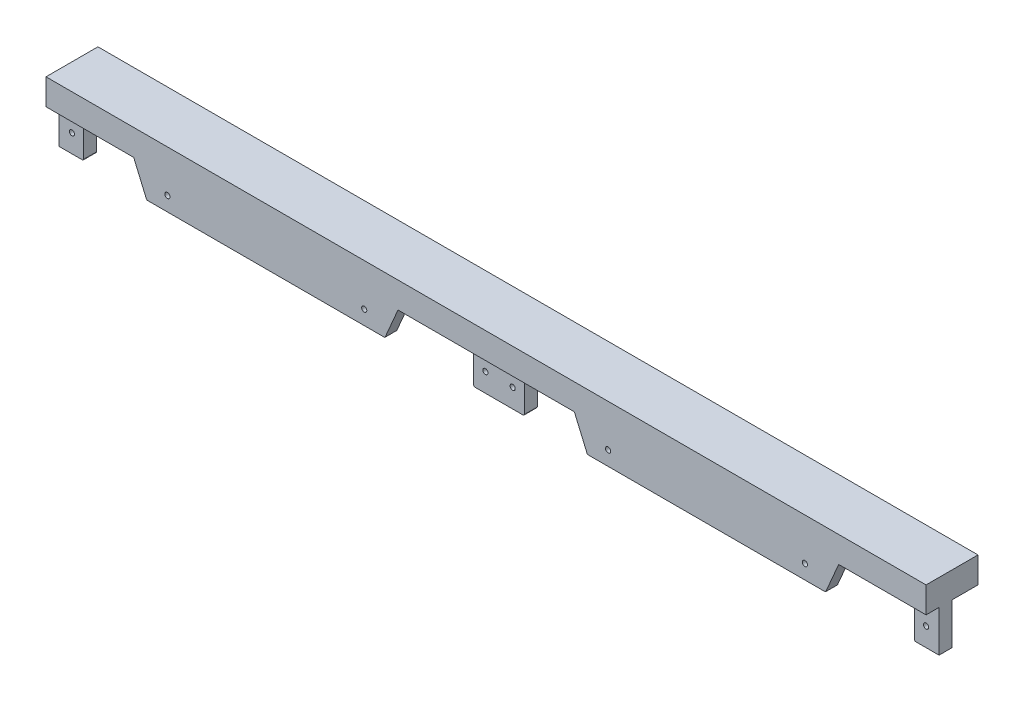
SolidWorks part; units mm, degrees
ref_plane "Front Plane" through (0, 0, 0) normal (0, 0, 1) x (1, 0, 0)
ref_plane "Top Plane" through (0, 0, 0) normal (0, 1, 0) x (1, 0, 0)
ref_plane "Right Plane" through (0, 0, 0) normal (1, 0, 0) x (0, 0, -1)
sketch "Sketch7" plane through (0, 0, 0) normal (0, 0, 1) x (1, 0, 0)
  line L0 (28.5374, 16.3338) -> (-22.3526, 16.3338)
  line L2 (-34.737, 8.48) -> (-39.2367, 8.48)
  line L3 (-34.4835, 16.3338) -> (-34.4835, 8.7336)
  line L4 (28.5374, 16.3338) -> (26.0523, 10.5507)
  line L5 (25.8166, 10.4804) -> (-19.6769, 10.4804)
  line L6 (-39.2367, 16.3338) -> (-34.4835, 16.3338)
  line L7 (-34.4835, 16.3338) -> (-22.3526, 16.3338)
  line L8 (28.5374, 16.3338) -> (40.6116, 16.3338)
  line L9 (113.3874, 16.3338) -> (62.4974, 16.3338)
  line L10 (-19.91, 10.6341) -> (-22.3526, 16.3338)
  line L11 (40.6116, 8.6159) -> (40.6116, 16.3338)
  line L12 (130.2133, 16.3338) -> (125.4616, 16.3338)
  line L14 (50.3665, 16.3338) -> (50.3665, 8.6159)
  line L15 (113.3874, 16.3338) -> (110.9023, 10.5507)
  line L16 (-39.2367, 16.3338) -> (-39.2367, 8.48)
  line L17 (110.6666, 10.4804) -> (65.1731, 10.4804)
  line L18 (50.113, 8.3623) -> (40.8651, 8.3623)
  line L19 (40.6116, 16.3338) -> (50.3665, 16.3338)
  line L20 (50.3665, 16.3338) -> (62.4974, 16.3338)
  line L22 (113.3874, 16.3338) -> (125.4616, 16.3338)
  line L23 (64.94, 10.6341) -> (62.4974, 16.3338)
  line L24 (125.4616, 8.6159) -> (125.4616, 16.3338)
  line L27 (130.2133, 8.3623) -> (125.7151, 8.3623)
  line L28 (130.2133, 8.3623) -> (130.2133, 16.3338)
  line L30 (-39.2367, 16.3338) -> (-39.2367, 21.3338)
  line L31 (-39.2367, 21.3338) -> (130.2133, 21.3338)
  line L35 (130.2133, 21.3338) -> (130.2133, 16.3338)
  arc A0 (-34.737, 8.48) -> (-34.4835, 8.7336) centre (-34.7371, 8.7336) ccw
  arc A1 (25.8166, 10.4804) -> (26.0523, 10.5507) centre (25.8713, 10.7274) ccw
  arc A2 (-19.91, 10.6341) -> (-19.6769, 10.4804) centre (-19.677, 10.7339) ccw
  arc A3 (50.113, 8.3623) -> (50.3665, 8.6159) centre (50.1129, 8.6159) ccw
  arc A4 (110.6666, 10.4804) -> (110.9023, 10.5507) centre (110.7213, 10.7274) ccw
  arc A5 (40.6116, 8.6159) -> (40.8651, 8.3623) centre (40.8652, 8.6159) ccw
  arc A6 (64.94, 10.6341) -> (65.1731, 10.4804) centre (65.173, 10.7339) ccw
  arc A7 (125.4616, 8.6159) -> (125.7151, 8.3623) centre (125.7152, 8.6159) ccw
  point P28 (28.3219, 15.8324)
  point P53 (28.248, -11.1747)
  point P54 (26.0201, -16.381)
  point P59 (-19.9035, -16.381)
  point P60 (-22.1569, -11.1751)
extrude "Boss-Extrude6" add sketch "Sketch7" against normal blind 2.25 contours L10 A2 L5 A1 L4 | L23 A6 L17 A4 L15 L9 region at (3.091, 13.4578, 0) region at (87.941, 13.4578, 0)
extrude "Boss-Extrude7" add sketch "Sketch7<12>" against normal blind 10 contours L35 L31 L30 L6 L7 L0 L8 L19 L20 L9 L22 L12 region at (45.4883, 18.8338, 0)
sketch "Sketch7<12>" plane through (0, 0, 0) normal (0, 0, 1) x (1, 0, 0) same geometry as "Sketch7"
extrude "Boss-Extrude8" add sketch "Sketch7<13>" against normal blind 2.5 from offset 2.5 contours L2 A0 L3 L6 L16 | L11 A5 L18 A3 L14 L19 | L24 A7 L27 L28 L12 region at (45.489, 12.3494, 0) region at (-36.8609, 12.4084, 0) region at (127.8383, 12.3495, 0) offset against normal yes
sketch "Sketch7<13>" plane through (0, 0, 0) normal (0, 0, 1) x (1, 0, 0) same geometry as "Sketch7"
sketch "Sketch8" plane through (0, 0, 0) normal (0, 0, 1) x (1, 0, 0)
  circle A0 centre (-36.7367, 11.9837) radius 0.5
  circle A1 centre (-15.8563, 13.2337) radius 0.5
  circle A2 centre (22.0353, 13.2337) radius 0.5
  circle A3 centre (42.8633, 11.9837) radius 0.5
  circle A4 centre (48.1133, 11.9837) radius 0.5
  circle A5 centre (68.9937, 13.2337) radius 0.5
  circle A6 centre (106.8853, 13.2337) radius 0.5
  circle A7 centre (127.7133, 11.9837) radius 0.5
extrude "Cut-Extrude1" cut sketch "Sketch8" against normal through all both and the other way through all
